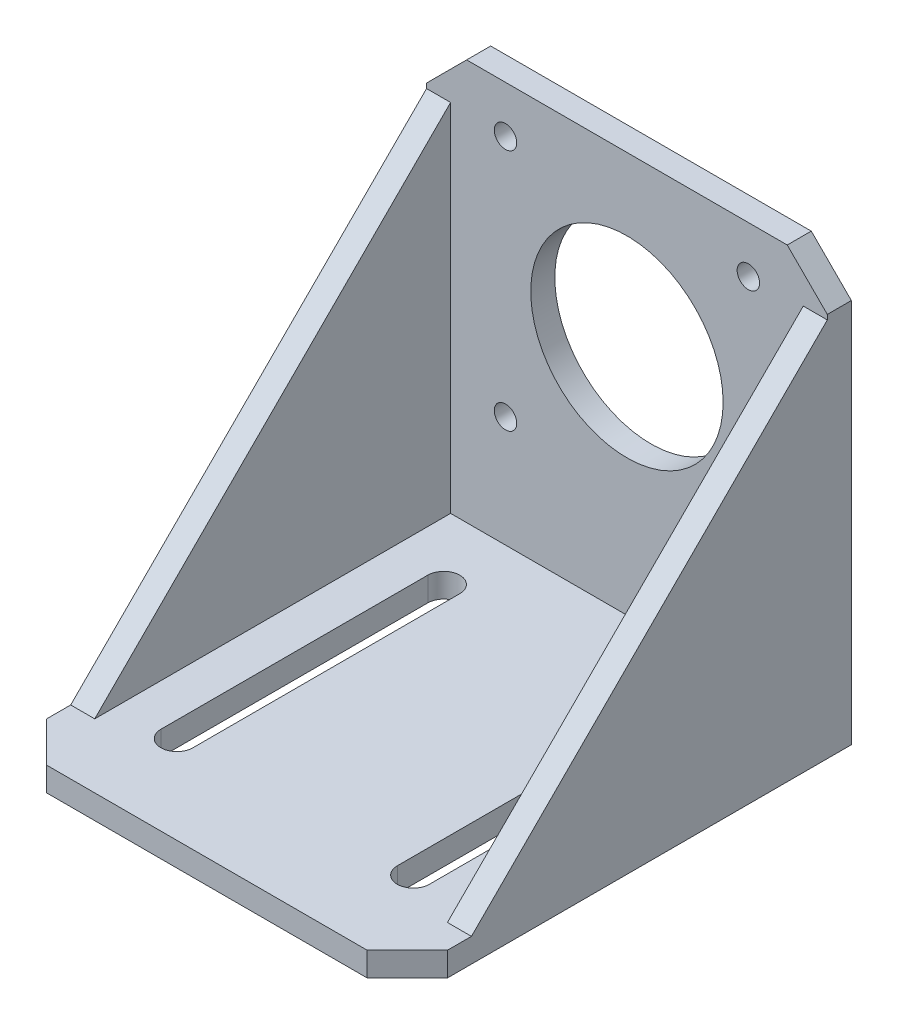
SolidWorks part; units mm, degrees
ref_plane "Alzado" through (0, 0, 0) normal (0, 0, 1) x (1, 0, 0)
ref_plane "Planta" through (0, 0, 0) normal (0, 1, 0) x (1, 0, 0)
ref_plane "Vista lateral" through (0, 0, 0) normal (1, 0, 0) x (0, 0, -1)
sketch "Croquis1" plane through (0, 0, 0) normal (0, 0, 1) x (1, 0, 0)
  line L0 (0, 12) -> (0, 21) construction
  line L1 (20, 21) -> (-20, 21)
  line L2 (-20, 21) -> (-25, 16)
  line L3 (-25, 16) -> (-25, -32)
  line L4 (-25, -32) -> (25, -32)
  line L5 (0, -32) -> (0, -12) construction
  line L6 (25, 16) -> (25, -32)
  line L7 (20, 21) -> (25, 16)
  circle A0 centre (0, 0) radius 12
  dimension "D2" = 12
  dimension "D1" = 53
  dimension "D5" = 25
  dimension "D6" = 135
  dimension "D7" = 20
extrude "Saliente-Extruir2" add sketch "Croquis1" along normal blind 3
sketch "Croquis2" plane through (0, 0, 3) normal (0, 0, 1) x (1, 0, 0)
  line L1 (-15.15, -15.15) -> (15.15, -15.15) construction
  line L2 (-15.15, -15.15) -> (-15.15, 15.15) construction
  line L3 (-15.15, 15.15) -> (15.15, 15.15) construction
  line L4 (15.15, -15.15) -> (15.15, 15.15) construction
  line L5 (-15.15, -15.15) -> (15.15, 15.15) construction
  line L6 (-15.15, 15.15) -> (15.15, -15.15) construction
  circle A0 centre (-15.15, 15.15) radius 1.4
  circle A1 centre (15.15, 15.15) radius 1.4
  circle A2 centre (15.15, -15.15) radius 1.4
  circle A3 centre (-15.15, -15.15) radius 1.4
  point P0 (0, 0)
  dimension "D3" = 2.8
  dimension "D1" = 30.3
  dimension "D2" = 30.3
extrude "Cortar-Extruir1" cut sketch "Croquis2" against normal through all
sketch "Croquis3" plane through (0, 0, 3) normal (0, 0, 1) x (1, 0, 0)
  line L0 (25, -32) -> (25, 16) construction
  line L1 (-25, -32) -> (25, -32)
  line L2 (-25, -32) -> (-25, -29)
  line L3 (-25, -29) -> (25, -29)
  line L4 (25, -32) -> (25, -29)
  dimension "D1" = 3
extrude "Saliente-Extruir3" add sketch "Croquis3" along normal blind 52.4
sketch "Croquis4" plane through (0, -32, 0) normal (0, -1, 0) x (1, 0, 0)
  line L0 (-25, 50.4) -> (-20, 55.4)
  line L1 (-25, 55.4) -> (-25, 0) construction
  line L2 (-25, 55.4) -> (25, 55.4) construction
  line L3 (-20, 55.4) -> (-25, 55.4)
  line L4 (-25, 55.4) -> (-25, 50.4)
  line L5 (-16.75, 44.4) -> (-16.75, 11.1)
  line L6 (-12.75, 44.4) -> (-12.75, 11.1)
  line L7 (25, 55.4) -> (-25, 55.4) construction
  line L8 (0, 55.4) -> (0, 0) construction
  line L9 (12.75, 44.4) -> (12.75, 11.1)
  line L10 (16.75, 44.4) -> (16.75, 11.1)
  line L11 (25, 55.4) -> (25, 50.4)
  line L12 (20, 55.4) -> (25, 55.4)
  line L13 (25, 50.4) -> (20, 55.4)
  arc A0 (-12.75, 44.4) -> (-16.75, 44.4) centre (-14.75, 44.4) ccw
  arc A1 (-16.75, 11.1) -> (-12.75, 11.1) centre (-14.75, 11.1) ccw
  arc A2 (16.75, 11.1) -> (12.75, 11.1) centre (14.75, 11.1) cw
  arc A3 (12.75, 44.4) -> (16.75, 44.4) centre (14.75, 44.4) cw
  point P6 (0, 55.4)
  point P15 (0, 55.4)
  dimension "D4" = 2
  dimension "D1" = 45
  dimension "D2" = 20
  dimension "D3" = 12.75
  dimension "D5" = 33.3
  dimension "D6" = 11
extrude "Cortar-Extruir2" cut sketch "Croquis4" against normal through all
sketch "Croquis5" plane through (-25, 0, 0) normal (-1, 0, 0) x (0, 0, 1)
  line L0 (3, 15.4) -> (3, -29)
  line L1 (3, 16) -> (3, -29) construction
  line L2 (3, -29) -> (47.4, -29)
  line L3 (50.4, -29) -> (3, -29) construction
  line L4 (47.4, -29) -> (3, 15.4)
  dimension "D1" = 45
  dimension "D2" = 3
extrude "Saliente-Extruir4" add sketch "Croquis5" against normal blind 3
mirror "Simetría1" about plane through (0, 0, 0) normal (1, 0, 0) of "Saliente-Extruir4"
